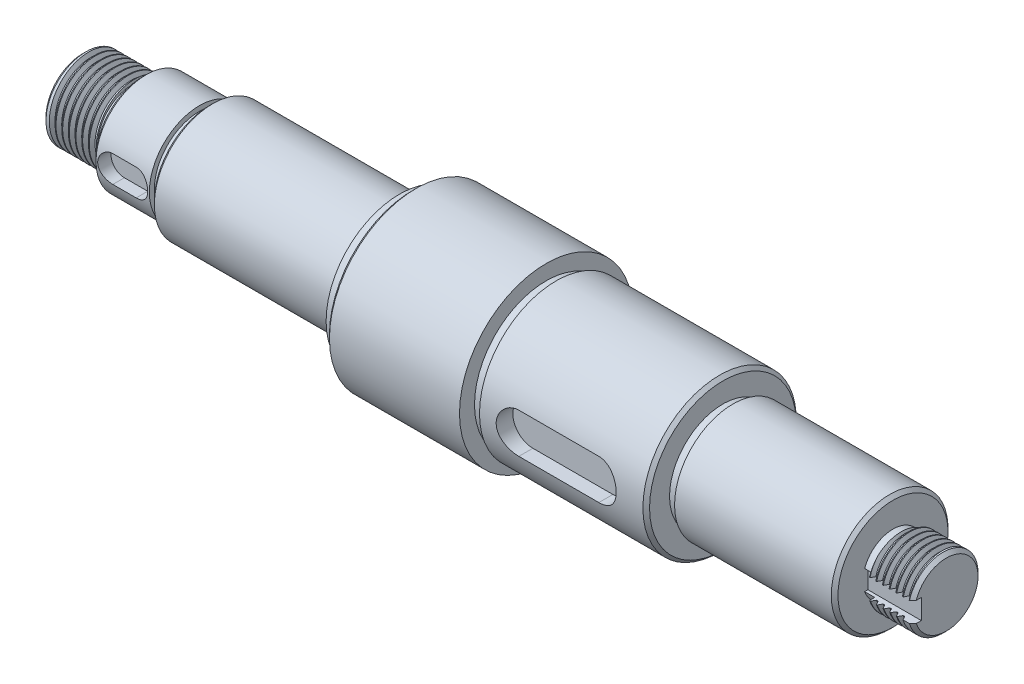
SolidWorks part; units mm, degrees
ref_plane "前视基准面" through (0, 0, 0) normal (0, 0, 1) x (1, 0, 0)
ref_plane "上视基准面" through (0, 0, 0) normal (0, 1, 0) x (1, 0, 0)
ref_plane "右视基准面" through (0, 0, 0) normal (1, 0, 0) x (0, 0, -1)
sketch "草图1" plane through (0, 0, 0) normal (0, 0, 1) x (1, 0, 0)
  line L0 (-286.3907, 34.2818) -> (152.9756, 34.2818) construction
  line L1 (-212.025, 46.2818) -> (-212.025, 34.2818)
  line L2 (-227.025, 34.2818) -> (-209.025, 34.2818)
  line L3 (-227.025, 34.2818) -> (-227.025, 45.2818)
  line L4 (-226.025, 46.2818) -> (-212.025, 46.2818)
  line L5 (-209.025, 34.2818) -> (-209.025, 46.5074)
  line L6 (-209.025, 34.2818) -> (-189.025, 34.2818)
  line L7 (-209.025, 34.2818) -> (-209.025, 48.2818)
  line L8 (-208.025, 49.2818) -> (-192.025, 49.2818)
  line L9 (-189.025, 34.2818) -> (-189.025, 49.2818)
  line L10 (-189.025, 34.2818) -> (-132.025, 34.2818)
  line L11 (-189.025, 34.2818) -> (-189.025, 50.7818)
  line L12 (-188.025, 51.7818) -> (-135.025, 51.7818)
  line L13 (-132.025, 34.2818) -> (-132.025, 51.7818)
  line L14 (-132.025, 34.2818) -> (-88.025, 34.2818)
  line L15 (-132.025, 34.2818) -> (-132.025, 56.2818)
  line L16 (-127.025, 60.2818) -> (-88.025, 60.2818)
  line L17 (-88.025, 34.2818) -> (-88.025, 60.2818)
  line L18 (-88.025, 34.2818) -> (-35.025, 34.2818)
  line L19 (-88.025, 34.2818) -> (-88.025, 57.2818)
  line L20 (-85.025, 57.2818) -> (-36.025, 57.2818)
  line L21 (-35.025, 34.2818) -> (-35.025, 56.2818)
  line L22 (-35.025, 34.2818) -> (15.975, 34.2818)
  line L23 (-35.025, 34.2818) -> (-35.025, 51.7818)
  line L24 (-32.025, 51.7818) -> (14.975, 51.7818)
  line L25 (15.975, 34.2818) -> (15.975, 50.7818)
  line L26 (15.975, 34.2818) -> (31.975, 34.2818)
  line L27 (15.975, 34.2818) -> (15.975, 42.8464)
  line L28 (18.975, 44.7818) -> (30.975, 44.7818)
  line L29 (31.975, 34.2818) -> (31.975, 43.7818)
  line L30 (-212.025, 44.7818) -> (-209.025, 44.7818)
  line L31 (-227.025, 45.2818) -> (-226.025, 46.2818)
  line L32 (-192.025, 49.2818) -> (-192.025, 34.2818)
  line L33 (-192.025, 34.2818) -> (-192.025, 47.7818)
  line L34 (-192.025, 47.7818) -> (-189.025, 47.7818)
  line L35 (-209.025, 48.2818) -> (-208.025, 49.2818)
  line L36 (-135.025, 51.7818) -> (-135.025, 34.2818)
  line L37 (-135.025, 34.2818) -> (-135.025, 50.2818)
  line L38 (-135.025, 50.2818) -> (-132.025, 50.2818)
  line L39 (-189.025, 50.7818) -> (-188.025, 51.7818)
  line L40 (-132.025, 56.2818) -> (-128.025, 56.2818)
  line L41 (-128.025, 59.2818) -> (-128.025, 34.2818)
  line L42 (-128.025, 59.2818) -> (-127.025, 60.2818)
  line L43 (-85.025, 57.2818) -> (-85.025, 34.2818)
  line L44 (-85.025, 34.2818) -> (-85.025, 55.7818)
  line L45 (-85.025, 55.7818) -> (-88.025, 55.7818)
  line L46 (-36.025, 57.2818) -> (-35.025, 56.2818)
  line L47 (-32.025, 51.7818) -> (-32.025, 34.2818)
  line L48 (-32.025, 34.2818) -> (-32.025, 50.2818)
  line L49 (-32.025, 50.2818) -> (-35.025, 50.2818)
  line L50 (14.975, 51.7818) -> (15.975, 50.7818)
  line L51 (18.975, 44.7818) -> (18.975, 34.2818)
  line L52 (18.975, 34.2818) -> (18.975, 43.2818)
  line L53 (18.975, 43.2818) -> (15.975, 43.2818)
  line L54 (30.975, 44.7818) -> (31.975, 43.7818)
  point P5 (-227.025, 46.2818)
  point P7 (-209.025, 49.2818)
  point P10 (-189.025, 51.7818)
  point P15 (-35.025, 57.2818)
  point P18 (15.975, 51.7818)
  point P21 (31.975, 44.7818)
  point P44 (-128.025, 60.2818)
  dimension "D1" = 12
  dimension "D2" = 18
  dimension "D3" = 3
  dimension "D4" = 1.5
  dimension "D5" = 15
  dimension "D6" = 20
  dimension "D8" = 3
  dimension "D9" = 1.5
  dimension "D10" = 17.5
  dimension "D11" = 57
  dimension "D13" = 3
  dimension "D14" = 1.5
  dimension "D15" = 44
  dimension "D16" = 26
  dimension "D18" = 4
  dimension "D19" = 22
  dimension "D20" = 53
  dimension "D21" = 23
  dimension "D23" = 3
  dimension "D24" = 1.5
  dimension "D25" = 17.5
  dimension "D26" = 51
  dimension "D28" = 16
  dimension "D29" = 1.5
  dimension "D31" = 3
  dimension "D32" = 10.5
  dimension "D33" = 3
  dimension "D34" = 1.5
revolve "旋转1" add sketch "草图1" angle 360 about L0
cosmetic thread "装饰螺纹线1" parameters "D2"=23
cosmetic thread "装饰螺纹线2" parameters "D2"=20
ref_plane "基准面1" through (0, 0, 15) normal (0, 0, 1) x (1, 0, 0)
sketch "草图2" plane through (0, 0, 15) normal (0, 0, 1) x (1, 0, 0)
  line L0 (-200.025, 49.2818) -> (-200.025, 19.2818) construction
  line L1 (-192.025, 49.2818) -> (-208.025, 49.2818) construction
  line L2 (-208.025, 19.2818) -> (-192.025, 19.2818) construction
  line L3 (-208.025, 34.2818) -> (-192.025, 34.2818) construction
  line L4 (-208.025, 49.2818) -> (-208.025, 19.2818) construction
  line L5 (-192.025, 19.2818) -> (-192.025, 49.2818) construction
  line L6 (-196.525, 34.2818) -> (-203.525, 34.2818) construction
  line L7 (-196.525, 30.2818) -> (-203.525, 30.2818)
  line L8 (-196.525, 38.2818) -> (-203.525, 38.2818)
  arc A0 (-196.525, 30.2818) -> (-196.525, 38.2818) centre (-196.525, 34.2818) ccw
  arc A1 (-203.525, 38.2818) -> (-203.525, 30.2818) centre (-203.525, 34.2818) ccw
  point P14 (-200.025, 34.2818)
  dimension "D2" = 15
  dimension "D1" = 8
extrude "切除-拉伸1" cut sketch "草图2" against normal blind 4 contours L8 A1 L7 A0
ref_plane "基准面2" through (0, 0, 23) normal (0, 0, 1) x (1, 0, 0)
sketch "草图3" plane through (0, 0, 23) normal (0, 0, 1) x (1, 0, 0)
  line L0 (-85.025, 34.2818) -> (-36.025, 34.2818) construction
  line L1 (-85.025, 57.2818) -> (-85.025, 11.2818) construction
  line L2 (-36.025, 57.2818) -> (-36.025, 11.2818) construction
  line L3 (-74.025, 34.2818) -> (-50.025, 34.2818) construction
  line L4 (-74.025, 40.2818) -> (-50.025, 40.2818)
  line L5 (-74.025, 28.2818) -> (-50.025, 28.2818)
  line L6 (-88.025, 8.2818) -> (-88.025, 60.2818) construction
  arc A0 (-74.025, 40.2818) -> (-74.025, 28.2818) centre (-74.025, 34.2818) ccw
  arc A1 (-50.025, 28.2818) -> (-50.025, 40.2818) centre (-50.025, 34.2818) ccw
  point P8 (-62.025, 34.2818)
  dimension "D2" = 36
  dimension "D1" = 8
  dimension "D3" = 12
extrude "切除-拉伸2" cut sketch "草图3" against normal blind 5 contours L5 A1 L4 A0
ref_plane "基准面3" through (0, 0, 10.5) normal (0, 0, 1) x (1, 0, 0)
sketch "草图4" plane through (0, 0, 10.5) normal (0, 0, 1) x (1, 0, 0)
  line L6 (15.975, 34.2818) -> (31.975, 34.2818) construction
  line L7 (15.975, 25.2818) -> (15.975, 43.2818) construction
  line L8 (31.975, 24.7818) -> (31.975, 43.7818) construction
  line L9 (31.975, 31.2818) -> (15.975, 31.2818)
  line L10 (31.975, 31.2818) -> (31.975, 37.2818)
  line L11 (15.975, 31.2818) -> (15.975, 37.2818)
  line L12 (31.975, 37.2818) -> (15.975, 37.2818)
  line L13 (31.975, 31.2818) -> (15.975, 37.2818) construction
  line L14 (15.975, 31.2818) -> (31.975, 37.2818) construction
  point P7 (23.975, 34.2818)
  dimension "D1" = 16
  dimension "D2" = 6
  dimension "D3" = 3
extrude "切除-拉伸3" cut sketch "草图4" against normal blind 3 contours L9 L10 L12 L11
thread "螺纹线4" pitch 2 start angle 0, offset 0, length 14, pitch 2, diameter 24
ref_plane "基准面7" through (-226.025, 34.2818, -12) normal (0, -1, 0) x (0, 0, -1)
sketch "螺纹线轮廓4" plane through (-226.025, 34.2818, -12) normal (0, -1, 0) x (0, 0, -1)
  line L0 (0, 0) -> (0, 2) construction
  line L11 (0, 0) -> (0, 1.75)
  line L12 (0, 1.75) -> (-1.0825, 1.125)
  line L13 (-1.0825, 1.125) -> (-1.0825, 0.625)
  line L15 (-1.0825, 0.625) -> (0, 0)
  line L17 (-1.0825, 0.875) -> (0, 0.875) construction
  point P2 (0, 0)
  dimension "Pitch" = 2
  dimension "Profile_Angle" = 60
  dimension "Profile_Land" = 0.5
  dimension "Profile_Height" = 1.0825
thread "螺纹线5" pitch 2 profile "螺纹线轮廓5" start angle 0, offset 0, length 12, pitch 2, diameter 21
ref_plane "基准面8" through (30.975, 34.2818, 10.5) normal (0, -1, 0) x (0, 0, 1)
sketch "螺纹线轮廓5" plane through (30.975, 34.2818, 10.5) normal (0, -1, 0) x (0, 0, 1)
  line L0 (0, 0) -> (0, 2) construction
  line L11 (0, 0) -> (0, 1.75)
  line L12 (0, 1.75) -> (-1.0825, 1.125)
  line L13 (-1.0825, 1.125) -> (-1.0825, 0.625)
  line L15 (-1.0825, 0.625) -> (0, 0)
  line L17 (-1.0825, 0.875) -> (0, 0.875) construction
  point P2 (0, 0)
  dimension "Pitch" = 2
  dimension "Profile_Angle" = 60
  dimension "Profile_Land" = 0.5
  dimension "Profile_Height" = 1.0825
